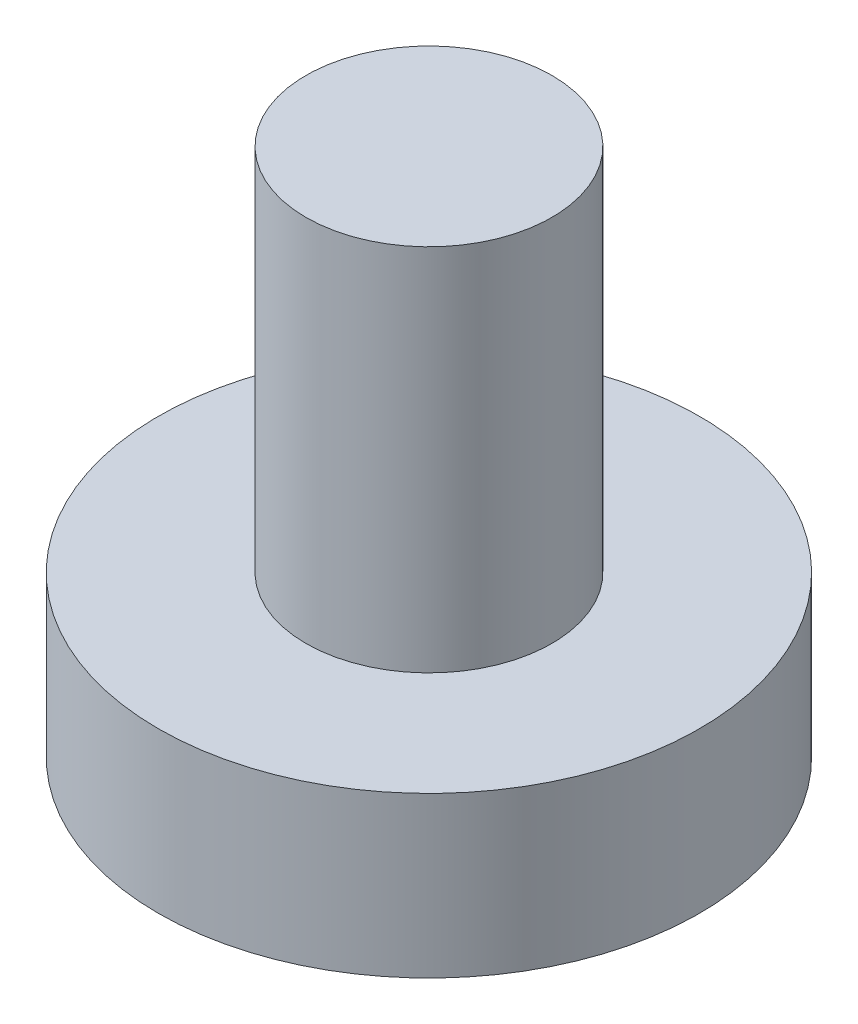
SolidWorks part; units mm, degrees
ref_plane "前视基准面" through (0, 0, 0) normal (0, 0, 1) x (1, 0, 0)
ref_plane "上视基准面" through (0, 0, 0) normal (0, 1, 0) x (1, 0, 0)
ref_plane "右视基准面" through (0, 0, 0) normal (1, 0, 0) x (0, 0, -1)
other "Configuration Table"
sketch "草图1" plane through (0, 0, 0) normal (0, 1, 0) x (1, 0, 0)
  line L1 (1.1547, 0) -> (0.5774, 1)
  line L2 (0.5774, 1) -> (-0.5774, 1)
  line L3 (-0.5774, 1) -> (-1.1547, 0)
  line L4 (-1.1547, 0) -> (-0.5774, -1)
  line L5 (-0.5774, -1) -> (0.5774, -1)
  line L6 (0.5774, -1) -> (1.1547, 0)
  circle A0 centre (0, 0) radius 2.2
  circle A1 centre (0, 0) radius 1 construction
  dimension "D1" = 4.4
  dimension "D2" = 2
extrude "凸台-拉伸1" add sketch "草图1" along normal blind 1.3 contours L5 L6 L1 L2 L3 L4 | A0 L6 L5 L4 L3 L2 L1 | L1 L2 L3 L4 L5 L6 | A0 region at (0, 0, 0) region at (-2.1378, 0, 0)
extrude "切除-拉伸1" cut sketch "草图1<3>" along normal blind 0.6 contours L5 L6 L1 L2 L3 L4 region at (0, 0, 0)
sketch "草图1<3>" plane through (0, 0, 0) normal (0, 1, 0) x (1, 0, 0) same geometry as "草图1"
sketch "草图2" plane through (0, 1.3, 0) normal (0, 1, 0) x (1, 0, 0)
  circle A0 centre (0, 0) radius 1
  dimension "D1" = 2
extrude "凸台-拉伸2" add sketch "草图2" along normal blind 3
